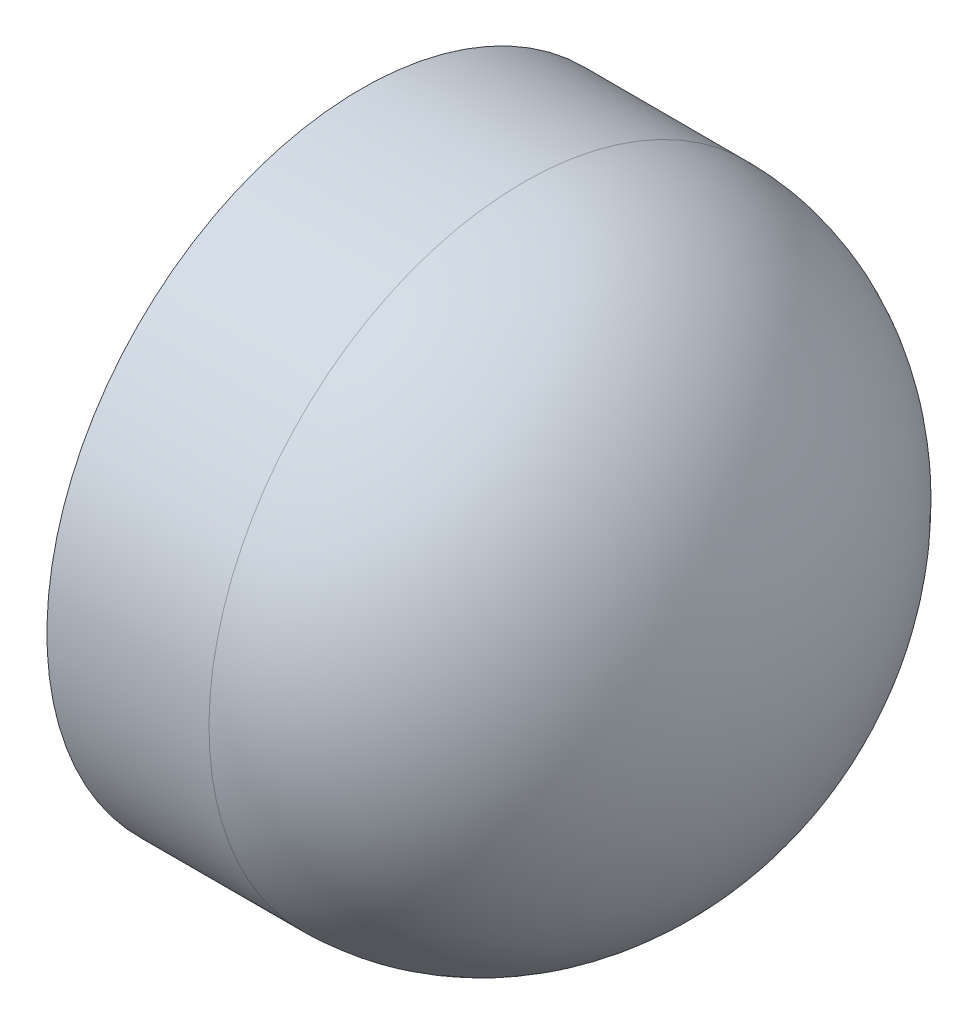
SolidWorks part; units mm, degrees
ref_plane "Front Plane" through (0, 0, 0) normal (0, 0, 1) x (1, 0, 0)
ref_plane "Top Plane" through (0, 0, 0) normal (0, 1, 0) x (1, 0, 0)
ref_plane "Right Plane" through (0, 0, 0) normal (1, 0, 0) x (0, 0, -1)
sketch "Sketch1" plane through (0, 0, 0) normal (1, 0, 0) x (0, 0, -1)
  circle A0 centre (-8.4919, 4.7851) radius 4.85
  dimension "D1" = 9.7
extrude "Boss-Extrude1" add sketch "Sketch1" along normal blind 2.5
dome "Dome1" faces to dome 1 distance 4 reverse direction no elliptical dome yes face at (2.5, 4.7851, 3.6419) parameters "D1"=4
shell "Shell1" thickness 0.6 removed face at (0, 4.7851, 3.6419)
sketch "Sketch4" plane through (0, 0, 0) normal (0, 1, 0) x (1, 0, 0)
  line L0 (0, -8.4919) -> (6.5, -8.4919) construction
  line L1 (0, -3.6419) -> (0, -13.3419) construction
  circle A0 centre (0, -8.4919) radius 1.5
  dimension "D1" = 3
extrude "Cut-Extrude2" cut sketch "Sketch4" along normal blind 4 and the other way blind 4
